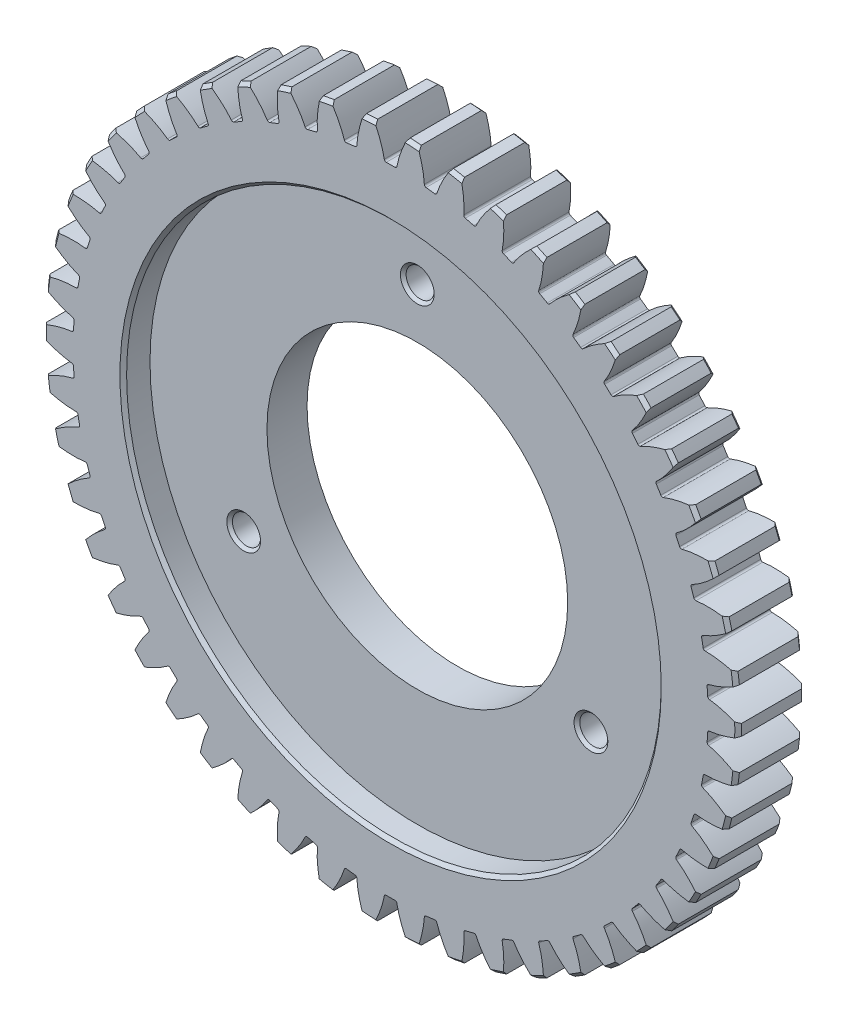
SolidWorks part; units mm, degrees
ref_plane "中间平面" through (0, 0, 0) normal (0, 0, 1) x (1, 0, 0)
ref_plane "上视基准面" through (0, 0, 0) normal (0, 1, 0) x (1, 0, 0)
ref_plane "右视基准面" through (0, 0, 0) normal (1, 0, 0) x (0, 0, -1)
sketch "直齿轮" plane through (0, 0, 0) normal (0, 0, 1) x (1, 0, 0)
  line L0 (0, 0) -> (-1.5705, 49.9753) construction
  line L2 (-0.8583, 46.9768) -> (0, 0)
  line L3 (0, 0) -> (0, 52) construction
  line L4 (1.5705, 49.9753) -> (0, 0) construction
  line L6 (0, 0) -> (0.8583, 46.9768)
  circle A0 centre (0, 0) radius 46.9846
  circle A1 centre (0, 0) radius 47.5
  arc A2 (1.5705, 49.9753) -> (-1.5705, 49.9753) centre (0, 0) ccw
  circle A3 centre (0, 0) radius 52
  spline S0 degree 4 poles (-0.8583, 46.9768) (-0.8591, 47.0215) (-0.8627, 47.1107) (-0.8774, 47.2888) (-0.9114, 47.5548) (-0.9634, 47.8631) (-1.0512, 48.2834) (-1.1738, 48.7694) (-1.3375, 49.3188) (-1.5479, 49.9285) (-1.8873, 50.8029) (-2.3957, 51.9244) (-3.1831, 53.3966) (-4.321, 55.1701) (-6.085, 57.5082) (-8.9914, 60.6451) (-13.2058, 64.156) (-18.9041, 67.6529) (-25.5044, 70.5369) (-32.4069, 72.5821) (-39.4937, 73.8344) (-47.0256, 74.3638) (-56.3705, 74.0437) (-67.3907, 72.2355) (-79.7562, 68.2868) (-91.0369, 62.6378) (-100.0387, 56.6817) (-108.4482, 49.9339) (-114.9346, 43.7045) (-120.8653, 36.9461) (-126.217, 29.7306) (-130.1437, 23.7114) (-133.7101, 17.4723) (-136.9122, 11.0388) (-139.3931, 5.261) (-141.2893, 0.2173) (-142.7161, -4.0395) (-143.7655, -7.4745) (-144.7229, -10.9362) (-145.5886, -14.422) (-146.3627, -17.9291) (-147.0456, -21.4554) (-147.6376, -24.9975) (-148.0764, -28.11) (-148.3962, -30.7836) (-148.6254, -33.018) (-148.7863, -34.8035) (-148.925, -36.5993) (-149.0413, -38.3814) (-149.1273, -40.0312) (-149.1885, -41.4781) (-149.2314, -42.8373) (-149.2589, -43.9054) (-149.2809, -45.3186) (-149.2888, -46.3272) (-149.2898, -47.9771) (-149.2726, -49.254) (-149.2437, -50.8034) (-149.1994, -52.196) (-149.1273, -54.0393) (-149.0315, -55.8247) (-148.9128, -57.6471) (-148.7709, -59.4448) (-148.6437, -60.8927) (-148.4674, -62.6927) (-148.2684, -64.4954) (-148.0468, -66.2915) (-147.8515, -67.7286) (-147.7493, -68.4453) (-147.6971, -68.8041) knots 0 0 0 0 0 0.000701 0.001401 0.002802 0.004203 0.005604 0.008133 0.010661 0.01319 0.015718 0.022839 0.02996 0.039347 0.048734 0.068727 0.096889 0.125051 0.153212 0.181374 0.209535 0.237696 0.271429 0.327752 0.384075 0.440398 0.46856 0.496721 0.553044 0.581206 0.609367 0.637529 0.66569 0.693852 0.722013 0.736094 0.750174 0.764255 0.778336 0.792417 0.806497 0.820578 0.834659 0.84874 0.85578 0.86282 0.869861 0.876901 0.883942 0.890982 0.895509 0.900036 0.904564 0.909091 0.914773 0.920455 0.926136 0.931818 0.9375 0.943182 0.954545 0.960227 0.965909 0.971591 0.977273 0.988636 0.994318 1 1 1 1 1 construction
  spline S1 degree 4 poles (-0.8583, 46.9768) (-0.8591, 47.0215) (-0.8627, 47.1107) (-0.8774, 47.2888) (-0.9114, 47.5548) (-0.9634, 47.8631) (-1.0512, 48.2834) (-1.1738, 48.7694) (-1.3375, 49.3188) (-1.5479, 49.9285) (-1.8873, 50.8029) (-2.3957, 51.9244) (-3.1831, 53.3966) (-4.321, 55.1701) (-6.085, 57.5082) (-8.9914, 60.6451) (-13.2058, 64.156) (-18.9041, 67.6529) (-25.5044, 70.5369) (-32.4069, 72.5821) (-39.4937, 73.8344) (-47.0256, 74.3638) (-56.3705, 74.0437) (-67.3907, 72.2355) (-79.7562, 68.2868) (-91.0369, 62.6378) (-100.0387, 56.6817) (-108.4482, 49.9339) (-114.9346, 43.7045) (-120.8653, 36.9461) (-126.217, 29.7306) (-130.1437, 23.7114) (-133.7101, 17.4723) (-136.9122, 11.0388) (-139.3931, 5.261) (-141.2893, 0.2173) (-142.7161, -4.0395) (-143.7655, -7.4745) (-144.7229, -10.9362) (-145.5886, -14.422) (-146.3627, -17.9291) (-147.0456, -21.4554) (-147.6376, -24.9975) (-148.0764, -28.11) (-148.3962, -30.7836) (-148.6254, -33.018) (-148.7863, -34.8035) (-148.925, -36.5993) (-149.0413, -38.3814) (-149.1273, -40.0312) (-149.1885, -41.4781) (-149.2314, -42.8373) (-149.2589, -43.9054) (-149.2744, -44.9018) (-149.2805, -45.4327) (-149.2828, -45.6951) knots 0 0 0 0 0 0.000701 0.001401 0.002802 0.004203 0.005604 0.008133 0.010661 0.01319 0.015718 0.022839 0.02996 0.039347 0.048734 0.068727 0.096889 0.125051 0.153212 0.181374 0.209535 0.237696 0.271429 0.327752 0.384075 0.440398 0.46856 0.496721 0.553044 0.581206 0.609367 0.637529 0.66569 0.693852 0.722013 0.736094 0.750174 0.764255 0.778336 0.792417 0.806497 0.820578 0.834659 0.84874 0.85578 0.86282 0.869861 0.876901 0.883942 0.890982 0.895509 0.900036 0.904564 0.909091 0.909091 0.909091 0.909091 0.909091
  spline S2 degree 4 poles (0.8583, 46.9768) (0.8591, 47.0215) (0.8627, 47.1107) (0.8774, 47.2888) (0.9114, 47.5548) (0.9634, 47.8631) (1.0512, 48.2834) (1.1738, 48.7694) (1.3375, 49.3188) (1.5479, 49.9285) (1.8873, 50.8029) (2.3957, 51.9244) (3.1831, 53.3966) (4.321, 55.1701) (6.085, 57.5082) (8.9914, 60.6451) (13.2058, 64.156) (18.9041, 67.6529) (25.5044, 70.5369) (32.4069, 72.5821) (39.4937, 73.8344) (47.0256, 74.3638) (56.3705, 74.0437) (67.3907, 72.2355) (79.7562, 68.2868) (91.0369, 62.6378) (100.0387, 56.6817) (108.4482, 49.9339) (114.9346, 43.7045) (120.8653, 36.9461) (126.217, 29.7306) (130.1437, 23.7114) (133.7101, 17.4723) (136.9122, 11.0388) (139.3931, 5.261) (141.2893, 0.2173) (142.7161, -4.0395) (143.7655, -7.4745) (144.7229, -10.9362) (145.5886, -14.422) (146.3627, -17.9291) (147.0456, -21.4554) (147.6376, -24.9975) (148.0764, -28.11) (148.3962, -30.7836) (148.6254, -33.018) (148.7863, -34.8035) (148.925, -36.5993) (149.0413, -38.3814) (149.1273, -40.0312) (149.1885, -41.4781) (149.2314, -42.8373) (149.2589, -43.9054) (149.2809, -45.3186) (149.2888, -46.3272) (149.2898, -47.9771) (149.2726, -49.254) (149.2437, -50.8034) (149.1994, -52.196) (149.1273, -54.0393) (149.0315, -55.8247) (148.9128, -57.6471) (148.7709, -59.4448) (148.6437, -60.8927) (148.4674, -62.6927) (148.2684, -64.4954) (148.0468, -66.2915) (147.8515, -67.7286) (147.7493, -68.4453) (147.6971, -68.8041) knots 0 0 0 0 0 0.000701 0.001401 0.002802 0.004203 0.005604 0.008133 0.010661 0.01319 0.015718 0.022839 0.02996 0.039347 0.048734 0.068727 0.096889 0.125051 0.153212 0.181374 0.209535 0.237696 0.271429 0.327752 0.384075 0.440398 0.46856 0.496721 0.553044 0.581206 0.609367 0.637529 0.66569 0.693852 0.722013 0.736094 0.750174 0.764255 0.778336 0.792417 0.806497 0.820578 0.834659 0.84874 0.85578 0.86282 0.869861 0.876901 0.883942 0.890982 0.895509 0.900036 0.904564 0.909091 0.914773 0.920455 0.926136 0.931818 0.9375 0.943182 0.954545 0.960227 0.965909 0.971591 0.977273 0.988636 0.994318 1 1 1 1 1 construction
  spline S3 degree 4 poles (0.8583, 46.9768) (0.8591, 47.0215) (0.8627, 47.1107) (0.8774, 47.2888) (0.9114, 47.5548) (0.9634, 47.8631) (1.0512, 48.2834) (1.1738, 48.7694) (1.3375, 49.3188) (1.5479, 49.9285) (1.8873, 50.8029) (2.3957, 51.9244) (3.1831, 53.3966) (4.321, 55.1701) (6.085, 57.5082) (8.9914, 60.6451) (13.2058, 64.156) (18.9041, 67.6529) (25.5044, 70.5369) (32.4069, 72.5821) (39.4937, 73.8344) (47.0256, 74.3638) (56.3705, 74.0437) (67.3907, 72.2355) (79.7562, 68.2868) (91.0369, 62.6378) (100.0387, 56.6817) (108.4482, 49.9339) (114.9346, 43.7045) (120.8653, 36.9461) (126.217, 29.7306) (130.1437, 23.7114) (133.7101, 17.4723) (136.9122, 11.0388) (139.3931, 5.261) (141.2893, 0.2173) (142.7161, -4.0395) (143.7655, -7.4745) (144.7229, -10.9362) (145.5886, -14.422) (146.3627, -17.9291) (147.0456, -21.4554) (147.6376, -24.9975) (148.0764, -28.11) (148.3962, -30.7836) (148.6254, -33.018) (148.7863, -34.8035) (148.925, -36.5993) (149.0413, -38.3814) (149.1273, -40.0312) (149.1885, -41.4781) (149.2314, -42.8373) (149.2589, -43.9054) (149.2744, -44.9018) (149.2805, -45.4327) (149.2828, -45.6951) knots 0 0 0 0 0 0.000701 0.001401 0.002802 0.004203 0.005604 0.008133 0.010661 0.01319 0.015718 0.022839 0.02996 0.039347 0.048734 0.068727 0.096889 0.125051 0.153212 0.181374 0.209535 0.237696 0.271429 0.327752 0.384075 0.440398 0.46856 0.496721 0.553044 0.581206 0.609367 0.637529 0.66569 0.693852 0.722013 0.736094 0.750174 0.764255 0.778336 0.792417 0.806497 0.820578 0.834659 0.84874 0.85578 0.86282 0.869861 0.876901 0.883942 0.890982 0.895509 0.900036 0.904564 0.909091 0.909091 0.909091 0.909091 0.909091
  dimension "基圆直径" = 93.9693
  dimension "齿根圆" = 95
  dimension "分度圆" = 100
  dimension "齿顶圆" = 104
  dimension "D1" = 3.1416
sketch "圆" plane through (0, 0, 0) normal (0, 0, 1) x (1, 0, 0)
  circle A0 centre (0, 0) radius 52 construction
  circle A1 centre (0, 0) radius 52
extrude "毛胚" add sketch "圆" along normal mid plane 10
chamfer "轮齿倒角" distance 0.5 angle 45 2 edges at (52, 0, -5) (52, 0, 5)
sketch "齿形" plane through (0, 0, 0) normal (0, 0, 1) x (1, 0, 0)
  line L4 (0, 0) -> (0.8583, 46.9768) construction
  line L5 (-0.8583, 46.9768) -> (0, 0) construction
  line L6 (0, 0) -> (0.8583, 46.9768)
  line L7 (-0.8583, 46.9768) -> (0, 0)
  circle A4 centre (0, 0) radius 47.5 construction
  circle A5 centre (0, 0) radius 52 construction
  circle A6 centre (0, 0) radius 47.5
  circle A7 centre (0, 0) radius 52
  spline S1 degree 4 poles (-998.3211, 29.695) (27.5289, 40.9407) (1.5082, 43.0307) (0.6251, 45.3103) (0.9114, 47.5548) (0.9634, 47.8631) (1.0512, 48.2834) (1.1738, 48.7694) (1.3375, 49.3188) (1.5479, 49.9285) (1.8873, 50.8029) (2.3957, 51.9244) (3.1831, 53.3966) (4.321, 55.1701) (6.085, 57.5082) (8.9914, 60.6451) (13.2058, 64.156) (18.9041, 67.6529) (25.5044, 70.5369) (32.4069, 72.5821) (39.4937, 73.8344) (47.0256, 74.3638) (56.3705, 74.0437) (67.3907, 72.2355) (79.7562, 68.2868) (91.0369, 62.6378) (100.0387, 56.6817) (108.4482, 49.9339) (114.9346, 43.7045) (120.8653, 36.9461) (126.217, 29.7306) (130.1437, 23.7114) (133.7101, 17.4723) (136.9122, 11.0388) (139.3931, 5.261) (141.2893, 0.2173) (142.7161, -4.0395) (143.7655, -7.4745) (144.7229, -10.9362) (145.5886, -14.422) (146.3627, -17.9291) (147.0456, -21.4554) (147.6376, -24.9975) (148.0764, -28.11) (148.3962, -30.7836) (148.6254, -33.018) (148.7863, -34.8035) (148.925, -36.5993) (149.0413, -38.3814) (149.1273, -40.0312) (149.1885, -41.4781) (149.2314, -42.8373) (149.3341, -46.8298) (149.3199, -54.7807) (148.6897, -6.0085) (157.5103, -1045.5619) knots -0.031272 -0.031272 -0.031272 -0.031272 -0.031272 0.000701 0.001401 0.002802 0.004203 0.005604 0.008133 0.010661 0.01319 0.015718 0.022839 0.02996 0.039347 0.048734 0.068727 0.096889 0.125051 0.153212 0.181374 0.209535 0.237696 0.271429 0.327752 0.384075 0.440398 0.46856 0.496721 0.553044 0.581206 0.609367 0.637529 0.66569 0.693852 0.722013 0.736094 0.750174 0.764255 0.778336 0.792417 0.806497 0.820578 0.834659 0.84874 0.85578 0.86282 0.869861 0.876901 0.883942 0.890982 0.895509 0.900036 0.904564 0.958675 0.958675 0.958675 0.958675 0.958675 only from (0.8583, 46.9768) to (149.2828, -45.6951) construction
  spline S3 degree 4 poles (998.3211, 29.695) (-27.5289, 40.9407) (-1.5082, 43.0307) (-0.6251, 45.3103) (-0.9114, 47.5548) (-0.9634, 47.8631) (-1.0512, 48.2834) (-1.1738, 48.7694) (-1.3375, 49.3188) (-1.5479, 49.9285) (-1.8873, 50.8029) (-2.3957, 51.9244) (-3.1831, 53.3966) (-4.321, 55.1701) (-6.085, 57.5082) (-8.9914, 60.6451) (-13.2058, 64.156) (-18.9041, 67.6529) (-25.5044, 70.5369) (-32.4069, 72.5821) (-39.4937, 73.8344) (-47.0256, 74.3638) (-56.3705, 74.0437) (-67.3907, 72.2355) (-79.7562, 68.2868) (-91.0369, 62.6378) (-100.0387, 56.6817) (-108.4482, 49.9339) (-114.9346, 43.7045) (-120.8653, 36.9461) (-126.217, 29.7306) (-130.1437, 23.7114) (-133.7101, 17.4723) (-136.9122, 11.0388) (-139.3931, 5.261) (-141.2893, 0.2173) (-142.7161, -4.0395) (-143.7655, -7.4745) (-144.7229, -10.9362) (-145.5886, -14.422) (-146.3627, -17.9291) (-147.0456, -21.4554) (-147.6376, -24.9975) (-148.0764, -28.11) (-148.3962, -30.7836) (-148.6254, -33.018) (-148.7863, -34.8035) (-148.925, -36.5993) (-149.0413, -38.3814) (-149.1273, -40.0312) (-149.1885, -41.4781) (-149.2314, -42.8373) (-149.3341, -46.8298) (-149.3199, -54.7807) (-148.6897, -6.0085) (-157.5103, -1045.5619) knots -0.031272 -0.031272 -0.031272 -0.031272 -0.031272 0.000701 0.001401 0.002802 0.004203 0.005604 0.008133 0.010661 0.01319 0.015718 0.022839 0.02996 0.039347 0.048734 0.068727 0.096889 0.125051 0.153212 0.181374 0.209535 0.237696 0.271429 0.327752 0.384075 0.440398 0.46856 0.496721 0.553044 0.581206 0.609367 0.637529 0.66569 0.693852 0.722013 0.736094 0.750174 0.764255 0.778336 0.792417 0.806497 0.820578 0.834659 0.84874 0.85578 0.86282 0.869861 0.876901 0.883942 0.890982 0.895509 0.900036 0.904564 0.958675 0.958675 0.958675 0.958675 0.958675 only from (-0.8583, 46.9768) to (-149.2828, -45.6951) construction
  spline S4 degree 4 poles (0.8583, 46.9768) (0.8591, 47.0215) (0.8627, 47.1107) (0.8774, 47.2888) (0.9114, 47.5548) (0.9634, 47.8631) (1.0512, 48.2834) (1.1738, 48.7694) (1.3375, 49.3188) (1.5479, 49.9285) (1.8873, 50.8029) (2.3957, 51.9244) (3.1831, 53.3966) (4.321, 55.1701) (6.085, 57.5082) (8.9914, 60.6451) (13.2058, 64.156) (18.9041, 67.6529) (25.5044, 70.5369) (32.4069, 72.5821) (39.4937, 73.8344) (47.0256, 74.3638) (56.3705, 74.0437) (67.3907, 72.2355) (79.7562, 68.2868) (91.0369, 62.6378) (100.0387, 56.6817) (108.4482, 49.9339) (114.9346, 43.7045) (120.8653, 36.9461) (126.217, 29.7306) (130.1437, 23.7114) (133.7101, 17.4723) (136.9122, 11.0388) (139.3931, 5.261) (141.2893, 0.2173) (142.7161, -4.0395) (143.7655, -7.4745) (144.7229, -10.9362) (145.5886, -14.422) (146.3627, -17.9291) (147.0456, -21.4554) (147.6376, -24.9975) (148.0764, -28.11) (148.3962, -30.7836) (148.6254, -33.018) (148.7863, -34.8035) (148.925, -36.5993) (149.0413, -38.3814) (149.1273, -40.0312) (149.1885, -41.4781) (149.2314, -42.8373) (149.2589, -43.9054) (149.2744, -44.9018) (149.2805, -45.4327) (149.2828, -45.6951) knots 0 0 0 0 0 0.000701 0.001401 0.002802 0.004203 0.005604 0.008133 0.010661 0.01319 0.015718 0.022839 0.02996 0.039347 0.048734 0.068727 0.096889 0.125051 0.153212 0.181374 0.209535 0.237696 0.271429 0.327752 0.384075 0.440398 0.46856 0.496721 0.553044 0.581206 0.609367 0.637529 0.66569 0.693852 0.722013 0.736094 0.750174 0.764255 0.778336 0.792417 0.806497 0.820578 0.834659 0.84874 0.85578 0.86282 0.869861 0.876901 0.883942 0.890982 0.895509 0.900036 0.904564 0.909091 0.909091 0.909091 0.909091 0.909091
  spline S5 degree 4 poles (-0.8583, 46.9768) (-0.8591, 47.0215) (-0.8627, 47.1107) (-0.8774, 47.2888) (-0.9114, 47.5548) (-0.9634, 47.8631) (-1.0512, 48.2834) (-1.1738, 48.7694) (-1.3375, 49.3188) (-1.5479, 49.9285) (-1.8873, 50.8029) (-2.3957, 51.9244) (-3.1831, 53.3966) (-4.321, 55.1701) (-6.085, 57.5082) (-8.9914, 60.6451) (-13.2058, 64.156) (-18.9041, 67.6529) (-25.5044, 70.5369) (-32.4069, 72.5821) (-39.4937, 73.8344) (-47.0256, 74.3638) (-56.3705, 74.0437) (-67.3907, 72.2355) (-79.7562, 68.2868) (-91.0369, 62.6378) (-100.0387, 56.6817) (-108.4482, 49.9339) (-114.9346, 43.7045) (-120.8653, 36.9461) (-126.217, 29.7306) (-130.1437, 23.7114) (-133.7101, 17.4723) (-136.9122, 11.0388) (-139.3931, 5.261) (-141.2893, 0.2173) (-142.7161, -4.0395) (-143.7655, -7.4745) (-144.7229, -10.9362) (-145.5886, -14.422) (-146.3627, -17.9291) (-147.0456, -21.4554) (-147.6376, -24.9975) (-148.0764, -28.11) (-148.3962, -30.7836) (-148.6254, -33.018) (-148.7863, -34.8035) (-148.925, -36.5993) (-149.0413, -38.3814) (-149.1273, -40.0312) (-149.1885, -41.4781) (-149.2314, -42.8373) (-149.2589, -43.9054) (-149.2744, -44.9018) (-149.2805, -45.4327) (-149.2828, -45.6951) knots 0 0 0 0 0 0.000701 0.001401 0.002802 0.004203 0.005604 0.008133 0.010661 0.01319 0.015718 0.022839 0.02996 0.039347 0.048734 0.068727 0.096889 0.125051 0.153212 0.181374 0.209535 0.237696 0.271429 0.327752 0.384075 0.440398 0.46856 0.496721 0.553044 0.581206 0.609367 0.637529 0.66569 0.693852 0.722013 0.736094 0.750174 0.764255 0.778336 0.792417 0.806497 0.820578 0.834659 0.84874 0.85578 0.86282 0.869861 0.876901 0.883942 0.890982 0.895509 0.900036 0.904564 0.909091 0.909091 0.909091 0.909091 0.909091
extrude "插齿" cut sketch "齿形" against normal mid plane 10 contours S5 A6 S4 A7 region at (0, 50.1155, 0)
fillet "圆角1" radius 0.3 2 edges at (0.9048, 47.4914, 0) (-0.9048, 47.4914, 0)
pattern_circular "圆周阵列1" count 50 over 360 about axis through (0, 0, 5) along (0, 0, -1) of "插齿", "圆角1"
fillet "圆角2" [suppressed] radius 0.3
pattern_circular "圆周阵列2" [suppressed] count 50 over 360 of bodies 165
sketch "分度圆" plane through (0, 0, 0) normal (0, 0, 1) x (1, 0, 0)
  circle A0 centre (0, 0) radius 50 construction
  circle A1 centre (0, 0) radius 50 construction
sketch "草图1" plane through (0, 0, 5) normal (0, 0, 1) x (1, 0, 0)
  circle A0 centre (0, 0) radius 40
  dimension "D1" = 80
extrude "切除-拉伸1" cut sketch "草图1" against normal blind 4
sketch "草图2" plane through (0, 0, 1) normal (0, 0, 1) x (1, 0, 0)
  circle A0 centre (0, 0) radius 22.5
  dimension "D1" = 45
extrude "切除-拉伸2" cut sketch "草图2" against normal through all
sketch "草图3" plane through (0, 0, 1) normal (0, 0, 1) x (1, 0, 0)
  circle A0 centre (0, 0) radius 30 construction
  point P3 (0, 30)
  point P4 (25.9808, -15)
  point P7 (-25.9808, -15)
  dimension "D1" = 60
  dimension "D2" = 3
hole_wizard "M5 螺纹孔1" positions "草图3" profile "草图4" tap size "M5" standard "GB" end condition up to next
sketch "草图4" plane through (-25.9808, -15, 1) normal (1, 0, 0) x (0, -1, 0)
  line L0 (0, 0) -> (0, 6)
  line L1 (0, 6) -> (2.1, 6)
  line L2 (2.1, 6) -> (2.1, 0.425)
  line L3 (2.1, 0.425) -> (2.525, 0)
  line L5 (2.525, 0) -> (0, 0)
  line L6 (-2.1, 0.425) -> (-2.525, 0) construction
  line L11 (0, -6.35) -> (0, 107.95) construction
  dimension "通孔螺纹孔钻头直径" = 4.2
  dimension "通孔螺纹孔钻头深度" = 6
  dimension "近端锥形沉头孔直径" = 5.05
  dimension "近端锥形沉头孔角度" = 90
cosmetic thread "孔螺纹线1" parameters "D2"=5
cosmetic thread "孔螺纹线2" parameters "D2"=5
cosmetic thread "孔螺纹线3" parameters "D2"=5
chamfer "倒角1" distance 0.5 angle 45 1 edges at (40, 0, 5)
equation "\"m\"= 2'模数"
equation "\"z\" = 50'齿数"
equation "\"a\"= 20'压力角（常见为20°）"
equation "\"B\" = 10'齿宽"
equation "\"C1\"= 0.5'轮齿倒角（若设为0，则无倒角）"
equation "\"x\"= 0'变位系数（不懂勿动）"
equation "\"ha\"= 1'齿顶高系数（不懂勿动）"
equation "\"c\"= 0.25'顶隙系数（不懂勿动）"
equation "\"基圆直径@直齿轮\"= \"m\" * \"z\" * cos ( \"a\" )"
equation "\"齿根圆@直齿轮\" = \"m\" * ( \"z\" - 2 * ( \"ha\" - \"x\" + \"c\" ) )"
equation "\"分度圆@直齿轮\"=\"m\" * \"z\""
equation "\"齿顶圆@直齿轮\" = \"m\" * ( \"z\" + 2 * ( \"ha\" + \"x\" ) )"
equation "\"R\"= 0.3'齿根圆角"
equation "\"D1\"= \"R\""
equation "\"D1@毛胚\" = \"B\""
equation "\"D1@轮齿倒角\" = IIF ( \"C1\" > 0 , \"C1\" , 0.001 )"
equation "\"轮齿倒角\"= IIF ( \"C1\" > 0 , \"unsuppressed\" , \"suppressed\" )"
equation "\"D1@插齿\" = \"B\""
equation "\"D1@圆周阵列1\" = \"z\""
equation "\"D1@直齿轮\"= \"m\" * ( pi / 2 ) - 2 * \"m\" * tan ( \"a\" ) * \"x\"'作者：机械菌-"
equation "\"D1@圆角1\"=\"R\""
equation "\"圆角1\" = IIF ( \"m\" * ( \"z\" - 2 * ( \"ha\" - \"x\" + \"c\" ) ) > \"m\" * \"z\" * cos ( \"a\" ) , \"unsuppressed\" , \"suppressed\" )"
equation "\"圆周阵列1\"= IIF ( \"m\" * ( \"z\" - 2 * ( \"ha\" - \"x\" + \"c\" ) ) > \"m\" * \"z\" * cos ( \"a\" ) , \"unsuppressed\" , \"suppressed\" )"
equation "\"D1@圆角2\"=\"R\""
equation "\"D1@圆周阵列2\" = \"z\""
equation "\"圆角2\" = IIF ( \"m\" * ( \"z\" - 2 * ( \"ha\" - \"x\" + \"c\" ) ) < \"m\" * \"z\" * cos ( \"a\" ) , \"unsuppressed\" , \"suppressed\" )"
equation "\"圆周阵列2\"= IIF ( \"m\" *  ( \"z\" - 2 *  ( \"ha\" - \"x\" + \"c\" )  )  < \"m\" * \"z\" * cos ( \"a\" )  ,  unsuppressed  ,  suppressed  ) "
